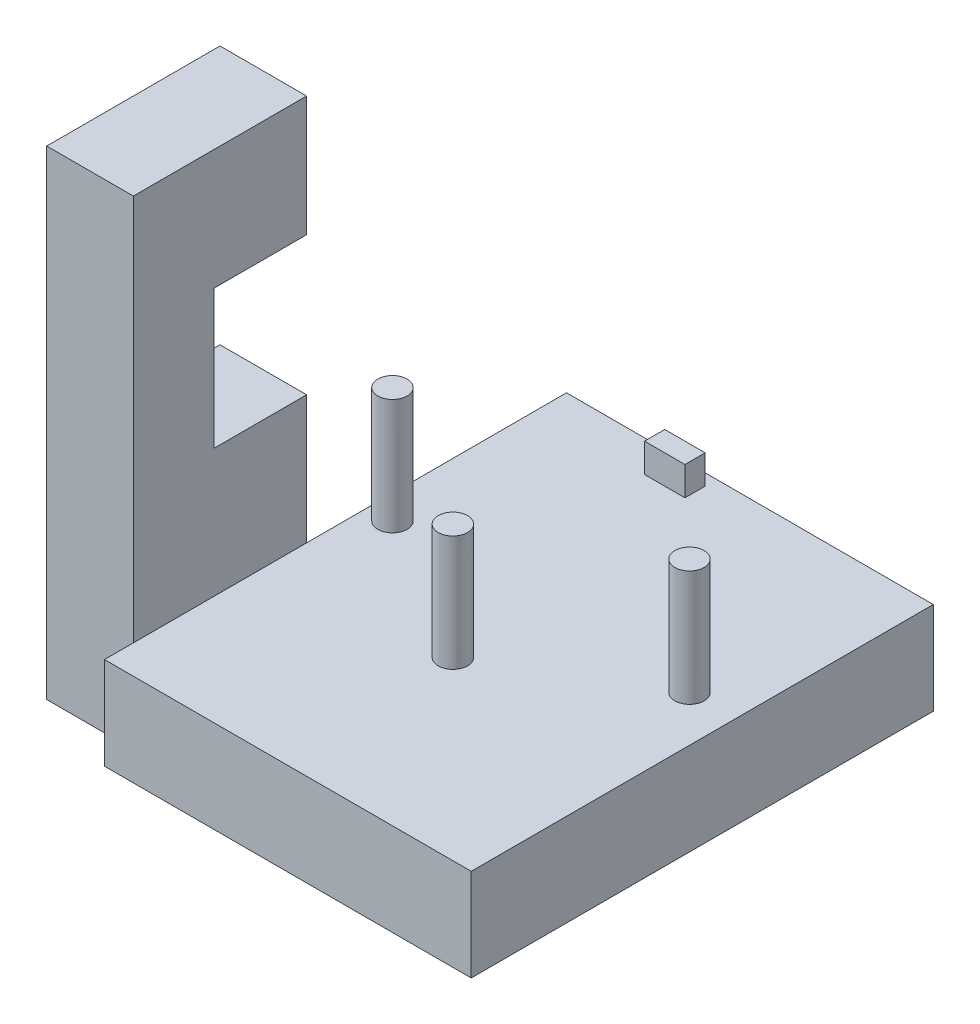
SolidWorks part; units mm, degrees
ref_plane "Front Plane" through (0, 0, 0) normal (0, 0, 1) x (1, 0, 0)
ref_plane "Top Plane" through (0, 0, 0) normal (0, 1, 0) x (1, 0, 0)
ref_plane "Right Plane" through (0, 0, 0) normal (1, 0, 0) x (0, 0, -1)
sketch "Sketch5" plane through (0, 0, 0) normal (0, 1, 0) x (1, 0, 0)
  line L1 (31.75, 40) -> (-31.75, 40)
  line L2 (31.75, 40) -> (31.75, -40)
  line L3 (31.75, -40) -> (-31.75, -40)
  line L4 (-31.75, 40) -> (-31.75, -40)
  line L5 (31.75, 40) -> (-31.75, -40) construction
  line L6 (31.75, -40) -> (-31.75, 40) construction
  point P0 (0, 0)
  dimension "D1" = 80
  dimension "D2" = 63.5
extrude "Boss-Extrude4" add sketch "Sketch5" along normal blind 16
sketch "Sketch6" plane through (0, 16, 0) normal (0, 1, 0) x (1, 0, 0)
  line L0 (31.75, 40) -> (-31.75, 40) construction
  line L1 (-5.75, 38) -> (-12.75, 38)
  line L2 (-5.75, 38) -> (-5.75, 34.5)
  line L3 (-5.75, 34.5) -> (-12.75, 34.5)
  line L4 (-12.75, 38) -> (-12.75, 34.5)
  line L5 (-5.75, 38) -> (-12.75, 34.5) construction
  line L6 (-5.75, 34.5) -> (-12.75, 38) construction
  line L9 (0, 0) -> (0, 40) construction
  line L10 (-31.75, 40) -> (-31.75, -40) construction
  point P0 (-9.25, 36.25)
  dimension "D1" = 7
  dimension "D2" = 3.5
  dimension "D3" = 2
  dimension "D4" = 19
extrude "Boss-Extrude5" add sketch "Sketch6" along normal blind 5 contours L3 L4 L1 L2
sketch "Sketch9" plane through (0, 0, 0) normal (0, 1, 0) x (1, 0, 0)
  line L0 (-31.75, 40) -> (-31.75, -40) construction
  line L5 (-31.75, -35) -> (-46.75, -35)
  line L6 (-31.75, -35) -> (-31.75, -5)
  line L7 (-31.75, -5) -> (-46.75, -5)
  line L8 (-46.75, -35) -> (-46.75, -5)
  line L9 (-31.75, -40) -> (31.75, -40) construction
  point P13 (-39.25, -5)
  dimension "D4" = 5
  dimension "D5" = 30
  dimension "D6" = 7.5
sketch "Sketch13" plane through (0, 16, 0) normal (0, 1, 0) x (1, 0, 0)
  line L0 (-31.75, 40) -> (-31.75, -40) construction
  line L2 (-31.75, -40) -> (31.75, -40) construction
  circle A0 centre (-27.6098, 5.72) radius 2.54
  circle A1 centre (23.8252, 5.72) radius 2.54
  circle A2 centre (-1.905, -9.52) radius 2.54
  dimension "D1" = 4.1402
  dimension "D3" = 5.08
  dimension "D4" = 51.435
  dimension "D6" = 5.08
  dimension "D7" = 5.08
  dimension "D2" = 45.72
  dimension "D5" = 45.72
  dimension "D8" = 25.7048
  dimension "D9" = 15.24
extrude "Boss-Extrude8" add sketch "Sketch13" along normal blind 20
extrude "Boss-Extrude10" add sketch "Sketch9" along normal blind 83 contours L8 L7 L6 L5
sketch "Sketch14" plane through (0, 0, 5) normal (0, 0, -1) x (-1, 0, 0)
  line L0 (31.75, 83) -> (31.75, 16) construction
  line L1 (31.75, 38.2) -> (46.75, 38.2)
  line L2 (31.75, 38.2) -> (31.75, 62.2)
  line L3 (31.75, 62.2) -> (46.75, 62.2)
  line L4 (46.75, 38.2) -> (46.75, 62.2)
  line L5 (46.75, 83) -> (46.75, 0) construction
  line L6 (31.75, 83) -> (46.75, 83) construction
  dimension "D1" = 20.8
  dimension "D2" = 24
extrude "Cut-Extrude1" cut sketch "Sketch14" against normal blind 16 contours L3 L4 L1 L2
